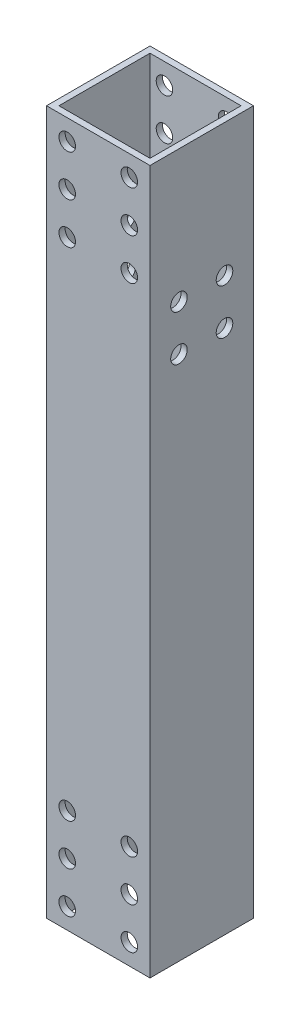
SolidWorks part; units mm, degrees
material "1060 Alloy"
ref_plane "Front Plane" through (0, 0, 0) normal (0, 0, 1) x (1, 0, 0)
ref_plane "Top Plane" through (0, 0, 0) normal (0, 1, 0) x (1, 0, 0)
ref_plane "Right Plane" through (0, 0, 0) normal (1, 0, 0) x (0, 0, -1)
sketch "Sketch1" plane through (0, 0, 0) normal (0, 1, 0) x (1, 0, 0)
  line L0 (0, 63.6278) -> (0, -69.3975) construction
  line L1 (-105.4586, 0) -> (105.4586, 0) construction
  line L2 (-11, 11) -> (-11, -11)
  line L3 (-12.5, 12.5) -> (12.5, 12.5)
  line L4 (-12.5, 12.5) -> (-12.5, -12.5)
  line L5 (-12.5, -12.5) -> (12.5, -12.5)
  line L6 (12.5, 12.5) -> (12.5, -12.5)
  line L7 (-11, -11) -> (11, -11)
  line L8 (11, 11) -> (11, -11)
  line L13 (-11, 11) -> (11, 11)
  point P5 (0, 0)
  dimension "D1" = 25
  dimension "D2" = 25
  dimension "D3" = 0
  dimension "D4" = 1.5
  dimension "D5" = 11
  dimension "D6" = 11
extrude "Boss-Extrude1" add sketch "Sketch1" along normal blind 85 and the other way blind 85
sketch "Sketch2" plane through (0, 0, -12.5) normal (0, 0, -1) x (-1, 0, 0)
  line L0 (0, 86.3155) -> (0, -83.2573) construction
  line L1 (-12.5, 85) -> (12.5, 85) construction
  circle A0 centre (7.5, 80) radius 2
  circle A1 centre (7.5, 70) radius 2
  circle A3 centre (-7.5, 80) radius 2
  circle A4 centre (-7.5, 70) radius 2
  circle A5 centre (7.5, 60) radius 2
  circle A6 centre (-7.5, 60) radius 2
  dimension "D1" = 7.5
  dimension "D5" = 10
  dimension "D2" = 7.5
  dimension "D3" = 7.5
  dimension "D4" = 7.5
  dimension "D6" = 10
  dimension "D7" = 5
  dimension "D8" = 10
  dimension "D9" = 7.5
  dimension "D10" = 5
  dimension "D11" = 10
  dimension "D12" = 7.5
extrude "Cut-Extrude1" cut sketch "Sketch2" against normal blind 25
mirror "Mirror1" about plane through (0, 0, 0) normal (0, 1, 0) of "Cut-Extrude1"
sketch "Sketch3" plane through (12.5, 0, 0) normal (1, 0, 0) x (0, 0, -1)
  line L0 (12.5, -85) -> (12.5, 85) construction
  line L1 (-12.5, 85) -> (12.5, 85) construction
  line L2 (-12.5, -85) -> (-12.5, 85) construction
  circle A0 centre (5.5, 53) radius 2
  circle A1 centre (5.5, 42) radius 2
  circle A2 centre (-5.5, 53) radius 2
  circle A3 centre (-5.5, 42) radius 2
  dimension "D1" = 7
  dimension "D2" = 32
  dimension "D3" = 32
  dimension "D4" = 7
  dimension "D5" = 11
  dimension "D6" = 11
  dimension "D7" = 7
  dimension "D8" = 7
extrude "Cut-Extrude2" cut sketch "Sketch3" against normal blind 25
